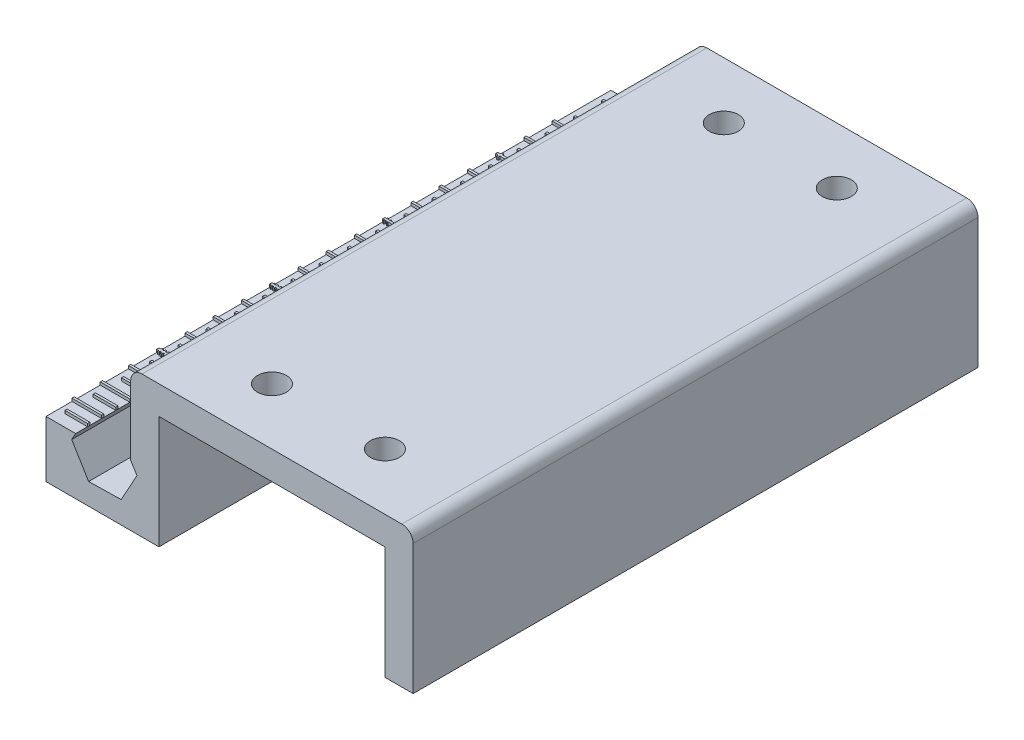
SolidWorks part; units mm, degrees
material "Printed PLA Orthotropic"
ref_plane "Front Plane" through (0, 0, 0) normal (0, 0, 1) x (1, 0, 0)
ref_plane "Top Plane" through (0, 0, 0) normal (0, 1, 0) x (1, 0, 0)
ref_plane "Right Plane" through (0, 0, 0) normal (1, 0, 0) x (0, 0, -1)
sketch "Sketch1" plane through (0, 0, 0) normal (0, 0, 1) x (1, 0, 0)
  line L0 (50.8, 0) -> (57.15, 0)
  line L2 (0, 0) -> (0, 25.4)
  line L3 (0, 25.4) -> (50.8, 25.4)
  line L4 (50.8, 0) -> (50.8, 25.4)
  line L5 (57.15, 0) -> (57.15, 29.21)
  line L6 (54.61, 31.75) -> (-3.81, 31.75)
  line L7 (0, 0) -> (-25.4, 0)
  line L8 (-8.4894, 4.9677) -> (-4.9553, 11.3921)
  line L9 (-4.9553, 11.3921) -> (-6.35, 13.6964)
  line L11 (-18.7306, 12.7) -> (-19.6169, 11.0888)
  line L12 (-19.6169, 11.0888) -> (-15.8202, 4.816)
  line L13 (-15.8202, 4.816) -> (-8.4894, 4.9677)
  line L14 (-25.4, 0) -> (-25.4, 12.7)
  line L15 (-6.35, 29.21) -> (-6.35, 13.6964)
  line L16 (-25.4, 12.7) -> (-18.7306, 12.7)
  line L17 (-8.752, 17.6649) -> (-12.4174, 17.5891) [skipped]
  arc A0 (57.15, 29.21) -> (54.61, 31.75) centre (54.61, 29.21) ccw
  arc A1 (-17.7185, 7.9524) -> (-6.7224, 8.1799) centre (-12.2861, 11.2405) ccw construction
  arc A2 (-3.81, 31.75) -> (-6.35, 29.21) centre (-3.81, 29.21) ccw
  point P10 (57.15, 31.75)
  point P27 (-6.35, 31.75)
  dimension "D6" = 2.54
  dimension "D8" = 12.7
  dimension "D12" = 2.54
  dimension "D1" = 50.8
  dimension "D2" = 25.4
  dimension "D3" = 63.5
  dimension "D4" = 31.75
  dimension "D5" = 6.35
  dimension "D9" = 25.4
  dimension "D10" = 18.0536
  dimension "D11" = 6.6694
extrude "Boss-Extrude2" add sketch "Sketch1" along normal blind 127
sketch "THE RULER" plane through (0, 0, 0) normal (0, 1, 0) x (1, 0, 0)
  line L0 (-25.4, -127) -> (-25.4, 0) construction
  line L4 (-18.7306, -6.35) -> (-18.7306, -6.858)
  line L5 (-25.4, 0) -> (0, 0) construction
  line L6 (-25.4, -6.35) -> (-25.4, -6.858)
  line L8 (-18.7306, -127) -> (-18.7306, 0) construction
  line L9 (-25.4, -12.7) -> (-18.7306, -12.7)
  line L10 (-25.4, -12.7) -> (-25.4, -13.208)
  line L11 (-25.4, -13.208) -> (-18.7306, -13.208)
  line L12 (-18.7306, -12.7) -> (-18.7306, -13.208)
  line L13 (-25.4, -19.05) -> (-18.7306, -19.05)
  line L14 (-25.4, -19.05) -> (-25.4, -19.558)
  line L15 (-25.4, -19.558) -> (-18.7306, -19.558)
  line L16 (-18.7306, -19.05) -> (-18.7306, -19.558)
  line L17 (-24.4237, -25.4) -> (-18.7306, -25.4)
  line L18 (-25.4, -25.4) -> (-24.8056, -25.4)
  line L19 (-25.4, -25.4) -> (-25.4, -25.908)
  line L20 (-25.4, -25.908) -> (-24.8056, -25.908)
  line L21 (-18.7306, -25.4) -> (-18.7306, -25.908)
  line L22 (-25.4, -32.258) -> (-18.7306, -32.258)
  line L23 (-25.4, -32.258) -> (-25.4, -31.75)
  line L24 (-25.4, -31.75) -> (-18.7306, -31.75)
  line L25 (-18.7306, -32.258) -> (-18.7306, -31.75)
  line L26 (-24.8056, -25.063) -> (-24.4237, -25.063)
  line L27 (-24.8056, -25.063) -> (-24.8056, -25.4)
  line L28 (-24.8056, -26.3147) -> (-24.4237, -26.3147)
  line L29 (-24.4237, -25.063) -> (-24.4237, -25.4)
  line L30 (-24.4237, -25.908) -> (-18.7306, -25.908)
  line L31 (-24.8056, -50.8) -> (-24.2974, -50.8)
  line L32 (-25.4, -38.1) -> (-18.7306, -38.1)
  line L33 (-25.4, -38.1) -> (-25.4, -38.608)
  line L34 (-25.4, -38.608) -> (-18.7306, -38.608)
  line L35 (-18.7306, -38.1) -> (-18.7306, -38.608)
  line L36 (-25.4, -44.45) -> (-18.7306, -44.45)
  line L37 (-25.4, -44.45) -> (-25.4, -44.958)
  line L38 (-25.4, -44.958) -> (-18.7306, -44.958)
  line L39 (-18.7306, -44.45) -> (-18.7306, -44.958)
  line L40 (-25.4, -50.8) -> (-25.0343, -50.8)
  line L41 (-25.4, -50.8) -> (-25.4, -51.308)
  line L42 (-25.4, -51.308) -> (-25.0343, -51.308)
  line L43 (-18.7306, -50.8) -> (-18.7306, -51.308)
  line L44 (-25.0343, -50.5475) -> (-24.8056, -50.5475)
  line L45 (-25.0343, -50.5475) -> (-25.0343, -50.8)
  line L46 (-25.0343, -51.584) -> (-24.8056, -51.584)
  line L47 (-24.8056, -50.5475) -> (-24.8056, -50.8)
  line L48 (-24.8056, -51.308) -> (-24.2974, -51.308)
  line L49 (-24.8056, -51.308) -> (-24.8056, -51.584)
  line L50 (-25.0343, -51.308) -> (-25.0343, -51.584)
  line L51 (-24.1534, -50.8) -> (-18.7306, -50.8)
  line L52 (-24.2974, -50.531) -> (-24.1534, -50.531)
  line L53 (-24.2974, -50.531) -> (-24.2974, -50.8)
  line L54 (-24.2974, -51.584) -> (-24.1534, -51.584)
  line L55 (-24.1534, -50.531) -> (-24.1534, -50.8)
  line L56 (-24.1534, -51.308) -> (-18.7306, -51.308)
  line L57 (-24.8056, -25.908) -> (-24.8056, -26.3147)
  line L58 (-24.4237, -25.908) -> (-24.4237, -26.3147)
  line L59 (-24.2974, -51.308) -> (-24.2974, -51.584)
  line L60 (-24.1534, -51.308) -> (-24.1534, -51.584)
  line L61 (-24.8056, -76.2) -> (-24.4237, -76.2)
  line L62 (-25.4, -57.15) -> (-18.7306, -57.15)
  line L63 (-25.4, -57.15) -> (-25.4, -57.658)
  line L64 (-25.4, -57.658) -> (-18.7306, -57.658)
  line L65 (-18.7306, -57.15) -> (-18.7306, -57.658)
  line L66 (-25.4, -63.5) -> (-18.7306, -63.5)
  line L67 (-25.4, -63.5) -> (-25.4, -64.008)
  line L68 (-25.4, -64.008) -> (-18.7306, -64.008)
  line L69 (-18.7306, -63.5) -> (-18.7306, -64.008)
  line L70 (-25.4, -69.85) -> (-18.7306, -69.85)
  line L71 (-25.4, -69.85) -> (-25.4, -70.358)
  line L72 (-25.4, -70.358) -> (-18.7306, -70.358)
  line L73 (-18.7306, -69.85) -> (-18.7306, -70.358)
  line L74 (-25.4, -76.2) -> (-25.0343, -76.2)
  line L75 (-25.4, -76.2) -> (-25.4, -76.708)
  line L76 (-25.4, -76.708) -> (-25.0343, -76.708)
  line L77 (-18.7306, -76.2) -> (-18.7306, -76.708)
  line L78 (-25.0343, -75.9757) -> (-24.8056, -75.9757)
  line L79 (-25.0343, -75.9757) -> (-25.0343, -76.2)
  line L80 (-25.0343, -76.995) -> (-24.8056, -76.995)
  line L81 (-24.8056, -75.9757) -> (-24.8056, -76.2)
  line L82 (-24.4237, -75.955) -> (-24.1534, -75.955)
  line L83 (-24.4237, -75.955) -> (-24.4237, -76.2)
  line L84 (-24.4237, -76.995) -> (-24.1534, -76.995)
  line L85 (-24.1534, -75.955) -> (-24.1534, -76.2)
  line L86 (-23.7034, -75.9188) -> (-23.4265, -75.9188)
  line L87 (-23.7034, -75.9188) -> (-23.7034, -76.2)
  line L88 (-23.7034, -76.995) -> (-23.4265, -76.995)
  line L89 (-23.4265, -75.9188) -> (-23.4265, -76.2)
  line L90 (-24.8056, -76.708) -> (-24.4237, -76.708)
  line L91 (-25.0343, -76.708) -> (-25.0343, -76.995)
  line L92 (-24.8056, -76.708) -> (-24.8056, -76.995)
  line L93 (-24.4237, -76.708) -> (-24.4237, -76.995)
  line L94 (-24.1534, -76.708) -> (-24.1534, -76.995)
  line L95 (-23.7034, -76.708) -> (-23.7034, -76.995)
  line L96 (-23.4265, -76.708) -> (-23.4265, -76.995)
  line L97 (-24.1534, -76.2) -> (-23.7034, -76.2)
  line L98 (-24.1534, -76.708) -> (-23.7034, -76.708)
  line L99 (-23.4265, -76.2) -> (-18.7306, -76.2)
  line L100 (-23.4265, -76.708) -> (-18.7306, -76.708)
  line L101 (-22.4683, -101.6) -> (-18.7306, -101.6)
  line L102 (-25.4, -82.55) -> (-18.7306, -82.55)
  line L103 (-25.4, -82.55) -> (-25.4, -83.058)
  line L104 (-25.4, -83.058) -> (-18.7306, -83.058)
  line L105 (-18.7306, -82.55) -> (-18.7306, -83.058)
  line L106 (-25.4, -89.408) -> (-18.7306, -89.408)
  line L107 (-25.4, -89.408) -> (-25.4, -88.9)
  line L108 (-25.4, -88.9) -> (-18.7306, -88.9)
  line L109 (-18.7306, -89.408) -> (-18.7306, -88.9)
  line L110 (-25.4, -95.25) -> (-18.7306, -95.25)
  line L111 (-25.4, -95.25) -> (-25.4, -95.758)
  line L112 (-25.4, -95.758) -> (-18.7306, -95.758)
  line L113 (-18.7306, -95.25) -> (-18.7306, -95.758)
  line L114 (-25.4, -101.6) -> (-24.9374, -101.6)
  line L115 (-25.4, -101.6) -> (-25.4, -102.108)
  line L116 (-25.4, -102.108) -> (-24.9374, -102.108)
  line L117 (-18.7306, -101.6) -> (-18.7306, -102.108)
  line L118 (-24.9374, -101.2815) -> (-24.6477, -101.2815)
  line L119 (-24.9374, -101.2815) -> (-24.9374, -101.6)
  line L120 (-24.9374, -102.394) -> (-24.6477, -102.394)
  line L121 (-24.6477, -101.2815) -> (-24.6477, -101.6)
  line L122 (-24.2974, -101.2815) -> (-23.9868, -101.2815)
  line L123 (-24.2974, -101.2815) -> (-24.2974, -101.6)
  line L124 (-24.2974, -102.4755) -> (-23.9868, -102.4755)
  line L125 (-23.9868, -101.2815) -> (-23.9868, -101.6)
  line L126 (-23.5885, -101.2476) -> (-23.2083, -101.2476)
  line L127 (-23.5885, -101.2476) -> (-23.5885, -101.6)
  line L128 (-23.5885, -102.4755) -> (-23.2083, -102.4755)
  line L129 (-23.2083, -101.2476) -> (-23.2083, -101.6)
  line L130 (-22.8018, -101.2646) -> (-22.4683, -101.2646)
  line L131 (-22.8018, -101.2646) -> (-22.8018, -101.6)
  line L132 (-22.8018, -102.4755) -> (-22.4683, -102.4755)
  line L133 (-22.4683, -101.2646) -> (-22.4683, -101.6)
  line L134 (-22.4683, -102.108) -> (-18.7306, -102.108)
  line L135 (-22.8018, -102.108) -> (-22.8018, -102.4755)
  line L136 (-22.4683, -102.108) -> (-22.4683, -102.4755)
  line L137 (-23.2083, -101.6) -> (-22.8018, -101.6)
  line L138 (-23.2083, -102.108) -> (-22.8018, -102.108)
  line L139 (-23.5885, -102.108) -> (-23.5885, -102.4755)
  line L140 (-23.2083, -102.108) -> (-23.2083, -102.4755)
  line L141 (-23.9868, -101.6) -> (-23.5885, -101.6)
  line L142 (-23.9868, -102.108) -> (-23.5885, -102.108)
  line L143 (-24.2974, -102.108) -> (-24.2974, -102.4755)
  line L144 (-23.9868, -102.108) -> (-23.9868, -102.4755)
  line L145 (-24.9374, -102.108) -> (-24.9374, -102.394)
  line L146 (-24.6477, -102.108) -> (-24.6477, -102.394)
  line L147 (-24.6477, -101.6) -> (-24.2974, -101.6)
  line L148 (-24.6477, -102.108) -> (-24.2974, -102.108)
  line L149 (-18.7306, -6.35) -> (-25.4, -6.35)
  line L150 (-25.4, -107.95) -> (-18.7306, -107.95)
  line L151 (-25.4, -107.95) -> (-25.4, -108.458)
  line L152 (-25.4, -108.458) -> (-18.7306, -108.458)
  line L153 (-18.7306, -107.95) -> (-18.7306, -108.458)
  line L154 (-25.4, -114.3) -> (-18.7306, -114.3)
  line L155 (-25.4, -114.3) -> (-25.4, -114.808)
  line L156 (-25.4, -114.808) -> (-18.7306, -114.808)
  line L157 (-18.7306, -114.3) -> (-18.7306, -114.808)
  line L158 (-25.4, -120.65) -> (-18.7306, -120.65)
  line L159 (-25.4, -120.65) -> (-25.4, -121.158)
  line L160 (-25.4, -121.158) -> (-18.7306, -121.158)
  line L161 (-18.7306, -120.65) -> (-18.7306, -121.158)
  line L162 (-23.8106, -47.625) -> (-18.7306, -47.625)
  line L163 (-23.8106, -3.175) -> (-18.7306, -3.175)
  line L164 (-23.8106, -3.175) -> (-23.8106, -3.683)
  line L165 (-23.8106, -3.683) -> (-18.7306, -3.683)
  line L166 (-18.7306, -3.175) -> (-18.7306, -3.683)
  line L167 (-23.8106, -9.525) -> (-18.7306, -9.525)
  line L168 (-23.8106, -9.525) -> (-23.8106, -10.033)
  line L169 (-23.8106, -10.033) -> (-18.7306, -10.033)
  line L170 (-18.7306, -9.525) -> (-18.7306, -10.033)
  line L171 (-23.8106, -15.875) -> (-18.7306, -15.875)
  line L172 (-23.8106, -15.875) -> (-23.8106, -16.383)
  line L173 (-23.8106, -16.383) -> (-18.7306, -16.383)
  line L174 (-18.7306, -15.875) -> (-18.7306, -16.383)
  line L175 (-23.8106, -22.225) -> (-18.7306, -22.225)
  line L176 (-23.8106, -22.225) -> (-23.8106, -22.733)
  line L177 (-23.8106, -22.733) -> (-18.7306, -22.733)
  line L178 (-18.7306, -22.225) -> (-18.7306, -22.733)
  line L179 (-23.8106, -28.575) -> (-18.7306, -28.575)
  line L180 (-23.8106, -28.575) -> (-23.8106, -29.083)
  line L181 (-23.8106, -29.083) -> (-18.7306, -29.083)
  line L182 (-18.7306, -28.575) -> (-18.7306, -29.083)
  line L183 (-23.8106, -34.925) -> (-18.7306, -34.925)
  line L184 (-23.8106, -34.925) -> (-23.8106, -35.433)
  line L185 (-23.8106, -35.433) -> (-18.7306, -35.433)
  line L186 (-18.7306, -34.925) -> (-18.7306, -35.433)
  line L187 (-23.8106, -41.275) -> (-18.7306, -41.275)
  line L188 (-23.8106, -41.275) -> (-23.8106, -41.783)
  line L189 (-23.8106, -41.783) -> (-18.7306, -41.783)
  line L190 (-18.7306, -41.275) -> (-18.7306, -41.783)
  line L191 (-23.8106, -47.625) -> (-23.8106, -48.133)
  line L192 (-23.8106, -48.133) -> (-18.7306, -48.133)
  line L193 (-18.7306, -47.625) -> (-18.7306, -48.133)
  line L194 (-23.8106, -53.975) -> (-18.7306, -53.975)
  line L195 (-23.8106, -53.975) -> (-23.8106, -54.483)
  line L196 (-23.8106, -54.483) -> (-18.7306, -54.483)
  line L197 (-18.7306, -53.975) -> (-18.7306, -54.483)
  line L198 (-23.8106, -60.325) -> (-18.7306, -60.325)
  line L199 (-23.8106, -60.325) -> (-23.8106, -60.833)
  line L200 (-23.8106, -60.833) -> (-18.7306, -60.833)
  line L201 (-18.7306, -60.325) -> (-18.7306, -60.833)
  line L202 (-23.8106, -66.675) -> (-18.7306, -66.675)
  line L203 (-23.8106, -66.675) -> (-23.8106, -67.183)
  line L204 (-23.8106, -67.183) -> (-18.7306, -67.183)
  line L205 (-18.7306, -66.675) -> (-18.7306, -67.183)
  line L206 (-23.8106, -73.025) -> (-18.7306, -73.025)
  line L207 (-23.8106, -73.025) -> (-23.8106, -73.533)
  line L208 (-23.8106, -73.533) -> (-18.7306, -73.533)
  line L209 (-18.7306, -73.025) -> (-18.7306, -73.533)
  line L210 (-23.8106, -79.375) -> (-18.7306, -79.375)
  line L211 (-23.8106, -79.375) -> (-23.8106, -79.883)
  line L212 (-23.8106, -79.883) -> (-18.7306, -79.883)
  line L213 (-18.7306, -79.375) -> (-18.7306, -79.883)
  line L214 (-23.8106, -85.725) -> (-18.7306, -85.725)
  line L215 (-23.8106, -85.725) -> (-23.8106, -86.233)
  line L216 (-23.8106, -86.233) -> (-18.7306, -86.233)
  line L217 (-18.7306, -85.725) -> (-18.7306, -86.233)
  line L218 (-23.8106, -92.075) -> (-18.7306, -92.075)
  line L219 (-23.8106, -92.075) -> (-23.8106, -92.583)
  line L220 (-23.8106, -92.583) -> (-18.7306, -92.583)
  line L221 (-18.7306, -92.075) -> (-18.7306, -92.583)
  line L222 (-23.8106, -98.425) -> (-18.7306, -98.425)
  line L223 (-23.8106, -98.425) -> (-23.8106, -98.933)
  line L224 (-23.8106, -98.933) -> (-18.7306, -98.933)
  line L225 (-18.7306, -98.425) -> (-18.7306, -98.933)
  line L226 (-23.8106, -104.775) -> (-18.7306, -104.775)
  line L227 (-23.8106, -104.775) -> (-23.8106, -105.283)
  line L228 (-23.8106, -105.283) -> (-18.7306, -105.283)
  line L229 (-18.7306, -104.775) -> (-18.7306, -105.283)
  line L230 (-23.8106, -111.125) -> (-18.7306, -111.125)
  line L231 (-23.8106, -111.125) -> (-23.8106, -111.633)
  line L232 (-23.8106, -111.633) -> (-18.7306, -111.633)
  line L233 (-18.7306, -111.125) -> (-18.7306, -111.633)
  line L234 (-23.8106, -117.475) -> (-18.7306, -117.475)
  line L235 (-23.8106, -117.475) -> (-23.8106, -117.983)
  line L236 (-23.8106, -117.983) -> (-18.7306, -117.983)
  line L237 (-18.7306, -117.475) -> (-18.7306, -117.983)
  line L238 (-23.8106, -123.825) -> (-18.7306, -123.825)
  line L239 (-23.8106, -123.825) -> (-23.8106, -124.333)
  line L240 (-23.8106, -124.333) -> (-18.7306, -124.333)
  line L241 (-18.7306, -123.825) -> (-18.7306, -124.333)
  line L242 (-18.7306, -6.858) -> (-25.4, -6.858)
  point P216 (-23.9284, -76.2)
  dimension "D2" = 0.508
  dimension "D3" = 6.35
  dimension "D4" = 0.508
  dimension "D5" = 6.35
  dimension "D6" = 6.35
  dimension "D7" = 0.508
  dimension "D8" = 0.508
  dimension "D9" = 6.35
  dimension "D10" = 0.508
  dimension "D11" = 6.35
  dimension "D12" = 0.508
  dimension "D13" = 6.35
  dimension "D14" = 0.508
  dimension "D15" = 6.35
  dimension "D16" = 0.508
  dimension "D17" = 6.35
  dimension "D18" = 0.508
  dimension "D19" = 6.35
  dimension "D20" = 0.508
  dimension "D21" = 6.35
  dimension "D22" = 0.508
  dimension "D23" = 6.35
  dimension "D24" = 0.508
  dimension "D25" = 6.35
  dimension "D26" = 0.508
  dimension "D27" = 6.35
  dimension "D28" = 0.508
  dimension "D29" = 6.35
  dimension "D30" = 0.508
  dimension "D31" = 6.35
  dimension "D32" = 0.508
  dimension "D33" = 6.35
  dimension "D34" = 0.508
  dimension "D35" = 6.35
  dimension "D36" = 0.508
  dimension "D37" = 6.35
  dimension "D38" = 0.508
  dimension "D39" = 6.35
  dimension "D40" = 5.08
  dimension "D41" = 0.508
  dimension "D42" = 3.175
  dimension "D43" = 5.08
  dimension "D44" = 0.508
  dimension "D45" = 5.08
  dimension "D46" = 3.175
  dimension "D47" = 0.508
  dimension "D48" = 5.08
  dimension "D49" = 3.175
  dimension "D50" = 0.508
  dimension "D51" = 5.08
  dimension "D52" = 3.175
  dimension "D53" = 0.508
  dimension "D54" = 3.175
  dimension "D55" = 5.08
  dimension "D56" = 0.508
  dimension "D57" = 3.175
  dimension "D58" = 5.08
  dimension "D59" = 0.508
  dimension "D60" = 3.175
  dimension "D61" = 0.508
  dimension "D62" = 5.08
  dimension "D63" = 3.175
  dimension "D64" = 0.508
  dimension "D65" = 3.175
  dimension "D66" = 0.508
  dimension "D67" = 5.08
  dimension "D68" = 5.08
  dimension "D69" = 3.175
  dimension "D70" = 5.08
  dimension "D71" = 0.508
  dimension "D72" = 5.08
  dimension "D73" = 3.175
  dimension "D74" = 0.508
  dimension "D75" = 5.08
  dimension "D76" = 3.175
  dimension "D77" = 0.508
  dimension "D78" = 5.08
  dimension "D79" = 3.175
  dimension "D80" = 0.508
  dimension "D81" = 3.175
  dimension "D82" = 5.08
  dimension "D83" = 0.508
  dimension "D84" = 5.08
  dimension "D85" = 3.175
  dimension "D86" = 0.508
  dimension "D87" = 5.08
  dimension "D88" = 3.175
  dimension "D89" = 0.508
  dimension "D90" = 5.08
  dimension "D91" = 3.175
  dimension "D92" = 0.508
  dimension "D93" = 5.08
  dimension "D94" = 3.175
  dimension "D95" = 0.508
  dimension "D96" = 5.08
  dimension "D97" = 3.175
  dimension "D98" = 0.508
  dimension "D99" = 3.175
extrude "Boss-Extrude6" add sketch "THE RULER" along normal blind 13.335 contours L12 L9 L10 L11 | L186 L183 L184 L185 | L60 L56 L43 L51 L55 L52 L53 L31 L47 L44 L45 L40 L41 L42 L50 L46 L49 L48 L59 L54 | L197 L194 L195 L196 | L65 L62 L63 L64 | L69 L66 L67 L68 | L73 L70 L71 L72 | L96 L100 L77 L99 L89 L86 L87 L97 L85 L82 L83 L61 L81 L78 L79 L74 L75 L76 L91 L80 L92 L90 L93 L84 L94 L98 L95 L88 | L225 L222 L223 L224 | L113 L110 L111 L112 | L221 L218 L219 L220 | L106 L109 L108 L107 | L217 L214 L215 L216 | L105 L102 L103 L104 | L213 L210 L211 L212 | L146 L148 L143 L124 L144 L142 L139 L128 L140 L138 L135 L132 L136 L134 L117 L101 L133 L130 L131 L137 L129 L126 L127 L141 L125 L122 L123 L147 L121 L118 L119 L114 L115 L116 L145 L120 | L229 L226 L227 L228 | L153 L150 L151 L152 | L233 L230 L231 L232 | L157 L154 L155 L156 | L237 L234 L235 L236 | L241 L238 L239 L240 | L161 L158 L159 L160 | L165 L166 L163 L164 | L169 L170 L167 L168 | L173 L174 L171 L172 | L15 L16 L13 L14 | L177 L178 L175 L176 | L17 L21 L30 L58 L28 L57 L20 L19 L18 L27 L26 L29 | L181 L182 L179 L180 | L24 L25 L22 L23 | L34 L35 L32 L33 | L189 L190 L187 L188 | L36 L39 L38 L37 | L162 L193 L192 L191 | L200 L201 L198 L199 | L204 L205 L202 L203 | L206 L209 L208 L207 region at (-22.0653, 0, 12.954) region at (-22.2087, 0, 51.0549) region at (-22.299, 0, 76.4577) region at (-22.0653, 0, 57.404) region at (-22.0653, 0, 63.754) region at (-22.0653, 0, 70.104) region at (-22.3964, 0, 101.8572) region at (-22.0653, 0, 82.804) region at (-22.0653, 0, 89.154) region at (-22.0653, 0, 95.504) region at (-22.0653, 0, 108.204) region at (-22.0653, 0, 114.554) region at (-22.0653, 0, 120.904) region at (-21.2706, 0, 35.179) region at (-21.2706, 0, 54.229) region at (-21.2706, 0, 79.629) region at (-21.2706, 0, 85.979) region at (-21.2706, 0, 92.329) region at (-21.2706, 0, 98.679) region at (-21.2706, 0, 105.029) region at (-21.2706, 0, 111.379) region at (-21.2706, 0, 117.729) region at (-21.2706, 0, 124.079)
sketch "Sketch9" plane through (0, 0, 127) normal (0, 0, 1) x (1, 0, 0)
  line L1 (-4.9553, 11.3921) -> (-8.752, 17.6649)
  line L2 (-8.752, 17.6649) -> (-16.0828, 17.5133)
  line L3 (-16.0828, 17.5133) -> (-19.6169, 11.0888)
  line L4 (-19.6169, 11.0888) -> (-15.8202, 4.816)
  line L5 (-15.8202, 4.816) -> (-8.4894, 4.9677)
  line L6 (-8.4894, 4.9677) -> (-4.9553, 11.3921)
  circle A0 centre (-12.2861, 11.2405) radius 6.35 construction
  dimension "D1" = 12.7
extrude "Cut-Extrude1" cut sketch "Sketch9" against normal blind 127
sketch "Sketch10" plane through (0, 31.75, 0) normal (0, 1, 0) x (1, 0, 0)
  line L0 (0, -63.5) -> (50.8, -63.5) construction
  line L4 (50.8, 0) -> (0, 0)
  line L5 (50.8, -127) -> (50.8, 0)
  line L6 (0, -127) -> (50.8, -127)
  line L7 (0, 0) -> (0, -127)
  line L8 (50.8, 0) -> (0, 0) construction
  line L9 (50.8, -127) -> (50.8, 0) construction
  line L10 (0, -127) -> (50.8, -127) construction
  line L11 (0, 0) -> (0, -127) construction
  circle A0 centre (12.7, -12.7) radius 3.2639
  circle A1 centre (38.1, -12.7) radius 3.2639
  circle A2 centre (38.1, -114.3) radius 3.2639
  circle A3 centre (12.7, -114.3) radius 3.2639
  dimension "D2" = 12.7
  dimension "D3" = 12.7
  dimension "D4" = 6.5278
  dimension "D5" = 6.5278
  dimension "D6" = 12.7
  dimension "D7" = 12.7
  dimension "D1" = 0
extrude "Cut-Extrude2" cut sketch "Sketch10" against normal through all
